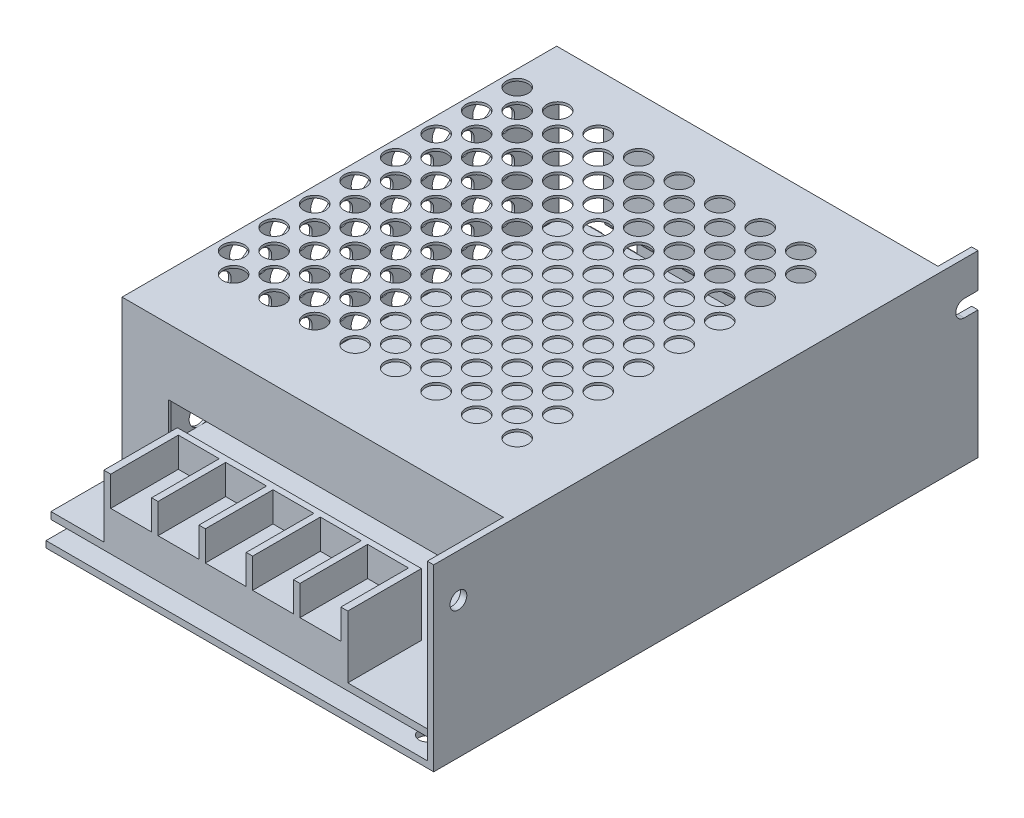
SolidWorks part; units mm, degrees
material "1060 Alloy"
ref_plane "Front Plane" through (0, 0, 0) normal (0, 0, 1) x (1, 0, 0)
ref_plane "Top Plane" through (0, 0, 0) normal (0, 1, 0) x (1, 0, 0)
ref_plane "Right Plane" through (0, 0, 0) normal (1, 0, 0) x (0, 0, -1)
sketch "Sketch1" plane through (0, 0, 0) normal (0, 0, 1) x (1, 0, 0)
  line L0 (0, 0) -> (0, 36.3)
  line L1 (0, 0) -> (-78.5, 0)
  line L2 (-78.5, 0) -> (-78.5, 1.3)
  line L3 (-78.5, 1.3) -> (-1.3, 1.3)
  line L4 (-1.3, 1.3) -> (-1.3, 36.3)
  line L5 (-1.3, 36.3) -> (0, 36.3)
  dimension "D1" = 1.3
  dimension "D2" = 36.3
  dimension "D3" = 78.5
extrude "Base Boss-Extrude1" add sketch "Sketch1" against normal blind 110.2
sketch "Sketch2" plane through (-1.3, 0, 0) normal (-1, 0, 0) x (0, 0, 1)
  line L0 (-110.2, 36.3) -> (0, 36.3) construction
  line L1 (0, 36.3) -> (0, 1.3) construction
  line L2 (-110.2, 36.3) -> (-110.2, 1.3) construction
  line L3 (-110.2, 29.3) -> (-107.4, 29.3)
  line L4 (-110.2, 29.3) -> (-110.2, 25.9)
  line L5 (-110.2, 25.9) -> (-107.4, 25.9)
  line L6 (-107.4, 29.3) -> (-107.4, 25.9) construction
  circle A0 centre (-5, 27.6) radius 1.7
  arc A1 (-107.4, 29.3) -> (-107.4, 25.9) centre (-107.4, 27.6) cw
  arc A2 (-107.4, 25.9) -> (-107.4, 29.3) centre (-107.4, 27.6) cw construction
  dimension "D1" = 3.4
  dimension "D2" = 7
  dimension "D3" = 3.3
  dimension "D4" = 3.4
  dimension "D5" = 7
  dimension "D6" = 4.5
extrude "Mounting Holes Side Cut-Extrude1" cut sketch "Sketch2" against normal up to surface (1.3 mm away) up to face at (0, 18.15, -55.1)
sketch "Sketch3" plane through (0, 1.3, 0) normal (0, 1, 0) x (1, 0, 0)
  line L0 (-1.3, 110.2) -> (-78.5, 110.2) construction
  line L1 (-72.7, 108.5) -> (-76.1, 108.5) construction
  line L2 (-72.7, 108.5) -> (-72.7, 110.2)
  line L3 (-72.7, 110.2) -> (-76.1, 110.2)
  line L4 (-76.1, 108.5) -> (-76.1, 110.2)
  line L5 (-78.5, 110.2) -> (-78.5, 0) construction
  line L7 (-5.8, 4.5) -> (-5.8, 0) construction
  line L8 (-1.3, 0) -> (-78.5, 0) construction
  line L9 (-5.8, 4.5) -> (-1.3, 4.5) construction
  line L10 (-1.3, 110.2) -> (-1.3, 0) construction
  circle A0 centre (-5.8, 4.5) radius 1.7
  arc A1 (-72.7, 108.5) -> (-76.1, 108.5) centre (-74.4, 108.5) cw
  arc A2 (-72.7, 108.5) -> (-76.1, 108.5) centre (-74.4, 108.5) ccw construction
  dimension "D1" = 3.4
  dimension "D2" = 2.8
  dimension "D3" = 2.8
  dimension "D4" = 106.8
  dimension "D5" = 2.4
extrude "Mounting Holes Bottom Cut-Extrude2" cut sketch "Sketch3" against normal up to surface (1.3 mm away) up to face at (-39.25, 0, -55.1)
sketch "Sketch4" plane through (-1.3, 0, 0) normal (-1, 0, 0) x (0, 0, 1)
  line L0 (-110.2, 36.3) -> (0, 36.3) construction
  line L1 (-110.2, 1.3) -> (-108.9, 1.3)
  line L2 (-110.2, 1.3) -> (-110.2, 8.3)
  line L3 (-110.2, 8.3) -> (-108.9, 8.3) construction
  line L4 (-108.9, 1.3) -> (-108.9, 8.3)
  line L5 (-103.4, 36.3) -> (-102.1, 36.3)
  line L6 (-103.4, 36.3) -> (-103.4, 12)
  line L7 (-103.4, 12) -> (-102.1, 12) construction
  line L8 (-102.1, 36.3) -> (-102.1, 12)
  line L9 (-108.8113, 10.1098) -> (-103.8252, 11.4459)
  line L10 (-108.4748, 8.8541) -> (-103.4887, 10.1902)
  line L11 (-106.3182, 10.7779) -> (-105.9818, 9.5221) construction
  line L12 (-110.2, 25.9) -> (-110.2, 1.3) construction
  arc A0 (-108.9, 8.3) -> (-108.4748, 8.8541) centre (-108.3263, 8.3) cw
  arc A1 (-110.2, 8.3) -> (-108.8113, 10.1098) centre (-108.3263, 8.3) cw
  arc A2 (-103.8252, 11.4459) -> (-103.4, 12) centre (-103.9737, 12) ccw
  arc A3 (-103.4887, 10.1902) -> (-102.1, 12) centre (-103.9737, 12) ccw
  dimension "D1" = 1.3
  dimension "D2" = 6.8
  dimension "D3" = 7
  dimension "D4" = 24.3
  dimension "D5" = 15
extrude "Heatsink Boss-Extrude2" add sketch "Sketch4" along normal blind 66.4
sketch "Sketch5" plane through (0, 0, -103.4) normal (0, 0, -1) x (-1, 0, 0)
  line L1 (1.3, 36.3) -> (78.5, 36.3)
  line L2 (1.3, 36.3) -> (1.3, 35.8)
  line L3 (1.3, 35.8) -> (78, 35.8)
  line L5 (78.5, 1.3) -> (78, 1.3)
  line L6 (78.5, 1.3) -> (78.5, 36.3)
  line L8 (78, 1.3) -> (78, 35.8)
  dimension "D1" = 0.5
extrude "Chassi Boss-Extrude3" add sketch "Sketch5" against normal blind 88
sketch "Sketch6" plane through (0, 0, -15.4) normal (0, 0, 1) x (1, 0, 0)
  line L1 (-1.3, 36.3) -> (-78.5, 36.3)
  line L2 (-1.3, 36.3) -> (-1.3, 23)
  line L3 (-1.3, 23) -> (-69.1, 23)
  line L6 (-78.5, 1.3) -> (-69.1, 1.3)
  line L7 (-78.5, 1.3) -> (-78.5, 36.3)
  line L9 (-69.1, 1.3) -> (-69.1, 23)
  dimension "D1" = 13.3
  dimension "D2" = 9.4
extrude "Chassi Front Boss-Extrude4" add sketch "Sketch6" against normal blind 0.5
ref_plane "PCB Plane1" through (0, 5, 0) normal (0, 1, 0) x (1, 0, 0)
sketch "Sketch7" plane through (0, 5, 0) normal (0, 1, 0) x (1, 0, 0)
  line L0 (-1.3, 108.9) -> (-1.3, 0) construction
  line L1 (-1.3, 0.5) -> (-78, 0.5)
  line L2 (-1.3, 0.5) -> (-1.3, 105)
  line L3 (-1.3, 105) -> (-78, 105)
  line L4 (-78, 0.5) -> (-78, 105)
  line L5 (-78, 15.9) -> (-78, 103.4) construction
  line L7 (-67.7, 110.2) -> (-72.7, 110.2) construction
  line L8 (-1.3, 0) -> (-78.5, 0) construction
  point P8 (-70.2, 110.2)
  dimension "D1" = 5.2
  dimension "D2" = 0.5
extrude "PCB Boss-Extrude5" add sketch "Sketch7" along normal blind 1.4
sketch "Sketch8" plane through (0, 6.4, 0) normal (0, 1, 0) x (1, 0, 0)
  line L0 (-78, 0.5) -> (-1.3, 0.5) construction
  line L1 (-67.3, 0.5) -> (-17.9, 0.5)
  line L2 (-67.3, 0.5) -> (-67.3, 15.4)
  line L3 (-67.3, 15.4) -> (-17.9, 15.4)
  line L4 (-17.9, 0.5) -> (-17.9, 15.4)
  line L5 (-78.5, 15.4) -> (-1.3, 15.4) construction
  line L6 (-1.3, 0.5) -> (-1.3, 105) construction
  line L7 (-78.5, 15.4) -> (-78.5, 0) construction
  dimension "D1" = 49.4
  dimension "D2" = 16.6
  dimension "D3" = 11.2
extrude "Connector Housing Boss-Extrude6" add sketch "Sketch8" along normal blind 12.6
sketch "Sketch9" plane through (0, 19, 0) normal (0, 1, 0) x (1, 0, 0)
  line L0 (-67.3, 0.5) -> (-17.9, 0.5) construction
  line L1 (-65.9, 0.5) -> (-57.62, 0.5)
  line L2 (-65.9, 0.5) -> (-65.9, 14.2)
  line L3 (-65.9, 14.2) -> (-57.62, 14.2)
  line L4 (-57.62, 0.5) -> (-57.62, 14.2)
  line L5 (-67.3, 14.2) -> (-65.9, 14.2) construction
  line L6 (-56.32, 14.2) -> (-48.04, 14.2)
  line L7 (-56.32, 14.2) -> (-56.32, 0.5)
  line L8 (-56.32, 0.5) -> (-48.04, 0.5)
  line L9 (-48.04, 14.2) -> (-48.04, 0.5)
  line L10 (-46.74, 0.5) -> (-38.46, 0.5)
  line L11 (-46.74, 0.5) -> (-46.74, 14.2)
  line L12 (-46.74, 14.2) -> (-38.46, 14.2)
  line L13 (-38.46, 0.5) -> (-38.46, 14.2)
  line L14 (-37.16, 14.2) -> (-28.88, 14.2)
  line L15 (-37.16, 14.2) -> (-37.16, 0.5)
  line L16 (-37.16, 0.5) -> (-28.88, 0.5)
  line L17 (-28.88, 14.2) -> (-28.88, 0.5)
  line L18 (-27.58, 14.2) -> (-19.3, 14.2)
  line L19 (-27.58, 14.2) -> (-27.58, 0.5)
  line L20 (-27.58, 0.5) -> (-19.3, 0.5)
  line L21 (-19.3, 14.2) -> (-19.3, 0.5)
  line L22 (-67.3, 15.4) -> (-67.3, 0.5) construction
  line L23 (-19.3, 14.2) -> (-17.9, 14.2) construction
  line L24 (-17.9, 0.5) -> (-17.9, 15.4) construction
  line L25 (-27.58, 14.2) -> (-28.88, 14.2) construction
  line L26 (-37.16, 14.2) -> (-38.46, 14.2) construction
  line L27 (-46.74, 14.2) -> (-48.04, 14.2) construction
  line L28 (-56.32, 14.2) -> (-57.62, 14.2) construction
  dimension "D1" = 1.3
  dimension "D2" = 1.4
  dimension "D3" = 13.7
extrude "Connector Screw Cut-Extrude3" cut sketch "Sketch9" against normal blind 6
sketch "Sketch10" plane through (0, 36.3, 0) normal (0, 1, 0) x (1, 0, 0)
  line L0 (-78.5, 92.2) -> (0, 92.2) construction
  line L1 (-78.5, 15.4) -> (-78.5, 103.4) construction
  line L2 (0, 110.2) -> (0, 0) construction
  line L3 (-75.3, 103.4) -> (-75.3, 15.4) construction
  line L4 (-78.5, 103.4) -> (-1.3, 103.4) construction
  line L5 (-78.5, 15.4) -> (-1.3, 15.4) construction
  line L6 (-75.3, 88.0988) -> (0, 88.0988) construction
  line L7 (-71.1988, 92.2) -> (-71.1988, 15.4) construction
  line L8 (-71.1988, 88.0988) -> (-75.3, 92.2) construction
  line L9 (-71.1988, 88.0988) -> (-67.0976, 92.2) construction
  line L10 (-71.1988, 88.0988) -> (-75.3, 83.9976) construction
  circle A0 centre (-75.3, 92.2) radius 2.2
  circle A1 centre (-71.1988, 88.0988) radius 2.2
  circle A2 centre (-67.0976, 92.2) radius 2.2
  circle A3 centre (-62.9963, 88.0988) radius 2.2
  circle A4 centre (-58.8951, 92.2) radius 2.2
  circle A5 centre (-54.7939, 88.0988) radius 2.2
  circle A6 centre (-50.6927, 92.2) radius 2.2
  circle A7 centre (-46.5915, 88.0988) radius 2.2
  circle A8 centre (-42.4902, 92.2) radius 2.2
  circle A9 centre (-38.389, 88.0988) radius 2.2
  circle A10 centre (-34.2878, 92.2) radius 2.2
  circle A11 centre (-30.1866, 88.0988) radius 2.2
  circle A12 centre (-26.0854, 92.2) radius 2.2
  circle A13 centre (-21.9841, 88.0988) radius 2.2
  circle A14 centre (-67.0976, 83.9976) radius 2.2
  circle A15 centre (-62.9963, 79.8963) radius 2.2
  circle A16 centre (-58.8951, 83.9976) radius 2.2
  circle A17 centre (-54.7939, 79.8963) radius 2.2
  circle A18 centre (-50.6927, 83.9976) radius 2.2
  circle A19 centre (-46.5915, 79.8963) radius 2.2
  circle A20 centre (-42.4902, 83.9976) radius 2.2
  circle A21 centre (-38.389, 79.8963) radius 2.2
  circle A22 centre (-34.2878, 83.9976) radius 2.2
  circle A23 centre (-30.1866, 79.8963) radius 2.2
  circle A24 centre (-26.0854, 83.9976) radius 2.2
  circle A25 centre (-21.9841, 79.8963) radius 2.2
  circle A26 centre (-67.0976, 75.7951) radius 2.2
  circle A27 centre (-62.9963, 71.6939) radius 2.2
  circle A28 centre (-58.8951, 75.7951) radius 2.2
  circle A29 centre (-54.7939, 71.6939) radius 2.2
  circle A30 centre (-50.6927, 75.7951) radius 2.2
  circle A31 centre (-46.5915, 71.6939) radius 2.2
  circle A32 centre (-42.4902, 75.7951) radius 2.2
  circle A33 centre (-38.389, 71.6939) radius 2.2
  circle A34 centre (-34.2878, 75.7951) radius 2.2
  circle A35 centre (-30.1866, 71.6939) radius 2.2
  circle A36 centre (-26.0854, 75.7951) radius 2.2
  circle A37 centre (-21.9841, 71.6939) radius 2.2
  circle A38 centre (-67.0976, 67.5927) radius 2.2
  circle A39 centre (-62.9963, 63.4915) radius 2.2
  circle A40 centre (-58.8951, 67.5927) radius 2.2
  circle A41 centre (-54.7939, 63.4915) radius 2.2
  circle A42 centre (-50.6927, 67.5927) radius 2.2
  circle A43 centre (-46.5915, 63.4915) radius 2.2
  circle A44 centre (-42.4902, 67.5927) radius 2.2
  circle A45 centre (-38.389, 63.4915) radius 2.2
  circle A46 centre (-34.2878, 67.5927) radius 2.2
  circle A47 centre (-30.1866, 63.4915) radius 2.2
  circle A48 centre (-26.0854, 67.5927) radius 2.2
  circle A49 centre (-21.9841, 63.4915) radius 2.2
  circle A50 centre (-67.0976, 59.3902) radius 2.2
  circle A51 centre (-62.9963, 55.289) radius 2.2
  circle A52 centre (-58.8951, 59.3902) radius 2.2
  circle A53 centre (-54.7939, 55.289) radius 2.2
  circle A54 centre (-50.6927, 59.3902) radius 2.2
  circle A55 centre (-46.5915, 55.289) radius 2.2
  circle A56 centre (-42.4902, 59.3902) radius 2.2
  circle A57 centre (-38.389, 55.289) radius 2.2
  circle A58 centre (-34.2878, 59.3902) radius 2.2
  circle A59 centre (-30.1866, 55.289) radius 2.2
  circle A60 centre (-26.0854, 59.3902) radius 2.2
  circle A61 centre (-21.9841, 55.289) radius 2.2
  circle A62 centre (-67.0976, 51.1878) radius 2.2
  circle A63 centre (-62.9963, 47.0866) radius 2.2
  circle A64 centre (-58.8951, 51.1878) radius 2.2
  circle A65 centre (-54.7939, 47.0866) radius 2.2
  circle A66 centre (-50.6927, 51.1878) radius 2.2
  circle A67 centre (-46.5915, 47.0866) radius 2.2
  circle A68 centre (-42.4902, 51.1878) radius 2.2
  circle A69 centre (-38.389, 47.0866) radius 2.2
  circle A70 centre (-34.2878, 51.1878) radius 2.2
  circle A71 centre (-30.1866, 47.0866) radius 2.2
  circle A72 centre (-26.0854, 51.1878) radius 2.2
  circle A73 centre (-21.9841, 47.0866) radius 2.2
  circle A74 centre (-67.0976, 42.9854) radius 2.2
  circle A75 centre (-62.9963, 38.8841) radius 2.2
  circle A76 centre (-58.8951, 42.9854) radius 2.2
  circle A77 centre (-54.7939, 38.8841) radius 2.2
  circle A78 centre (-50.6927, 42.9854) radius 2.2
  circle A79 centre (-46.5915, 38.8841) radius 2.2
  circle A80 centre (-42.4902, 42.9854) radius 2.2
  circle A81 centre (-38.389, 38.8841) radius 2.2
  circle A82 centre (-34.2878, 42.9854) radius 2.2
  circle A83 centre (-30.1866, 38.8841) radius 2.2
  circle A84 centre (-26.0854, 42.9854) radius 2.2
  circle A85 centre (-21.9841, 38.8841) radius 2.2
  circle A86 centre (-75.3, 83.9976) radius 2.2
  circle A87 centre (-71.1988, 79.8963) radius 2.2
  circle A88 centre (-75.3, 75.7951) radius 2.2
  circle A89 centre (-71.1988, 71.6939) radius 2.2
  circle A90 centre (-75.3, 67.5927) radius 2.2
  circle A91 centre (-71.1988, 63.4915) radius 2.2
  circle A92 centre (-75.3, 59.3902) radius 2.2
  circle A93 centre (-71.1988, 55.289) radius 2.2
  circle A94 centre (-75.3, 51.1878) radius 2.2
  circle A95 centre (-71.1988, 47.0866) radius 2.2
  circle A96 centre (-75.3, 42.9854) radius 2.2
  circle A97 centre (-71.1988, 38.8841) radius 2.2
  circle A98 centre (-75.3, 34.7829) radius 2.2
  circle A99 centre (-71.1988, 30.6817) radius 2.2
  circle A100 centre (-67.0976, 34.7829) radius 2.2
  circle A101 centre (-62.9963, 30.6817) radius 2.2
  circle A102 centre (-58.8951, 34.7829) radius 2.2
  circle A103 centre (-54.7939, 30.6817) radius 2.2
  circle A104 centre (-50.6927, 34.7829) radius 2.2
  circle A105 centre (-46.5915, 30.6817) radius 2.2
  circle A106 centre (-42.4902, 34.7829) radius 2.2
  circle A107 centre (-38.389, 30.6817) radius 2.2
  circle A108 centre (-34.2878, 34.7829) radius 2.2
  circle A109 centre (-30.1866, 30.6817) radius 2.2
  circle A110 centre (-26.0854, 34.7829) radius 2.2
  circle A111 centre (-21.9841, 30.6817) radius 2.2
  circle A112 centre (-17.8829, 92.2) radius 2.2
  circle A113 centre (-13.7817, 88.0988) radius 2.2
  circle A114 centre (-17.8829, 83.9976) radius 2.2
  circle A115 centre (-13.7817, 79.8963) radius 2.2
  circle A116 centre (-17.8829, 75.7951) radius 2.2
  circle A117 centre (-13.7817, 71.6939) radius 2.2
  circle A118 centre (-17.8829, 67.5927) radius 2.2
  circle A119 centre (-13.7817, 63.4915) radius 2.2
  circle A120 centre (-17.8829, 59.3902) radius 2.2
  circle A121 centre (-13.7817, 55.289) radius 2.2
  circle A122 centre (-17.8829, 51.1878) radius 2.2
  circle A123 centre (-13.7817, 47.0866) radius 2.2
  circle A124 centre (-17.8829, 42.9854) radius 2.2
  circle A125 centre (-13.7817, 38.8841) radius 2.2
  circle A126 centre (-17.8829, 34.7829) radius 2.2
  circle A127 centre (-13.7817, 30.6817) radius 2.2
  dimension "D1" = 4.4
  dimension "D2" = 1
  dimension "D3" = 9
  dimension "D5" = 1.4
  dimension "D4" = 45
  dimension "D6" = 8
  dimension "D7" = 8
sketch "Sketch11" plane through (-78.5, 0, 0) normal (-1, 0, 0) x (0, 0, 1)
  line L0 (-92.2, 36.3) -> (-92.2, 0) construction
  line L1 (-15.4, 36.3) -> (-103.4, 36.3) construction
  line L2 (-110.2, 0) -> (0, 0) construction
  line L3 (-103.4, 33.1) -> (-15.4, 33.1) construction
  line L4 (-103.4, 1.3) -> (-103.4, 36.3) construction
  line L5 (-15.4, 1.3) -> (-15.4, 36.3) construction
  line L6 (-88.0988, 36.3) -> (-88.0988, 0) construction
  line L7 (-103.4, 28.9988) -> (-15.4, 28.9988) construction
  line L8 (-88.0988, 33.1) -> (-92.2, 28.9988) construction
  line L10 (-88.0988, 33.1) -> (-83.9976, 28.9988) construction
  line L11 (-92.2, 28.9988) -> (-88.0988, 24.8976) construction
  circle A0 centre (-88.0988, 33.1) radius 2.2
  circle A1 centre (-92.2, 28.9988) radius 2.2
  circle A2 centre (-83.9976, 28.9988) radius 2.2
  circle A3 centre (-79.8963, 33.1) radius 2.2
  circle A4 centre (-75.7951, 28.9988) radius 2.2
  circle A5 centre (-71.6939, 33.1) radius 2.2
  circle A6 centre (-67.5927, 28.9988) radius 2.2
  circle A7 centre (-63.4915, 33.1) radius 2.2
  circle A8 centre (-59.3902, 28.9988) radius 2.2
  circle A9 centre (-55.289, 33.1) radius 2.2
  circle A10 centre (-51.1878, 28.9988) radius 2.2
  circle A11 centre (-47.0866, 33.1) radius 2.2
  circle A12 centre (-42.9854, 28.9988) radius 2.2
  circle A13 centre (-38.8841, 33.1) radius 2.2
  circle A14 centre (-34.7829, 28.9988) radius 2.2
  circle A15 centre (-30.6817, 33.1) radius 2.2
  circle A16 centre (-83.9976, 20.7963) radius 2.2
  circle A17 centre (-79.8963, 24.8976) radius 2.2
  circle A18 centre (-75.7951, 20.7963) radius 2.2
  circle A19 centre (-71.6939, 24.8976) radius 2.2
  circle A20 centre (-67.5927, 20.7963) radius 2.2
  circle A21 centre (-63.4915, 24.8976) radius 2.2
  circle A22 centre (-59.3902, 20.7963) radius 2.2
  circle A23 centre (-55.289, 24.8976) radius 2.2
  circle A24 centre (-51.1878, 20.7963) radius 2.2
  circle A25 centre (-47.0866, 24.8976) radius 2.2
  circle A26 centre (-42.9854, 20.7963) radius 2.2
  circle A27 centre (-38.8841, 24.8976) radius 2.2
  circle A28 centre (-34.7829, 20.7963) radius 2.2
  circle A29 centre (-30.6817, 24.8976) radius 2.2
  circle A30 centre (-83.9976, 12.5939) radius 2.2
  circle A31 centre (-79.8963, 16.6951) radius 2.2
  circle A32 centre (-75.7951, 12.5939) radius 2.2
  circle A33 centre (-71.6939, 16.6951) radius 2.2
  circle A34 centre (-67.5927, 12.5939) radius 2.2
  circle A35 centre (-63.4915, 16.6951) radius 2.2
  circle A36 centre (-59.3902, 12.5939) radius 2.2
  circle A37 centre (-55.289, 16.6951) radius 2.2
  circle A38 centre (-51.1878, 12.5939) radius 2.2
  circle A39 centre (-47.0866, 16.6951) radius 2.2
  circle A40 centre (-42.9854, 12.5939) radius 2.2
  circle A41 centre (-38.8841, 16.6951) radius 2.2
  circle A42 centre (-34.7829, 12.5939) radius 2.2
  circle A43 centre (-30.6817, 16.6951) radius 2.2
  circle A44 centre (-83.9976, 4.3915) radius 2.2
  circle A45 centre (-79.8963, 8.4927) radius 2.2
  circle A46 centre (-75.7951, 4.3915) radius 2.2
  circle A47 centre (-71.6939, 8.4927) radius 2.2
  circle A48 centre (-67.5927, 4.3915) radius 2.2
  circle A49 centre (-63.4915, 8.4927) radius 2.2
  circle A50 centre (-59.3902, 4.3915) radius 2.2
  circle A51 centre (-55.289, 8.4927) radius 2.2
  circle A52 centre (-51.1878, 4.3915) radius 2.2
  circle A53 centre (-47.0866, 8.4927) radius 2.2
  circle A54 centre (-42.9854, 4.3915) radius 2.2
  circle A55 centre (-38.8841, 8.4927) radius 2.2
  circle A56 centre (-34.7829, 4.3915) radius 2.2
  circle A57 centre (-30.6817, 8.4927) radius 2.2
  circle A58 centre (-92.2, 20.7963) radius 2.2
  circle A59 centre (-88.0988, 24.8976) radius 2.2
  circle A60 centre (-92.2, 12.5939) radius 2.2
  circle A61 centre (-88.0988, 16.6951) radius 2.2
  circle A62 centre (-92.2, 4.3915) radius 2.2
  circle A63 centre (-88.0988, 8.4927) radius 2.2
  dimension "D2" = 1.4
  dimension "D3" = 4.4
  dimension "D4" = 1
  dimension "D1" = 45
  dimension "D5" = 8
  dimension "D6" = 4
extrude "Chassi Venting Holes Top Cut-Extrude5" cut sketch "Sketch10" against normal up to surface (0.5 mm away) up to face at (-49, 35.8, -73.8)
extrude "Chassi Venting Holes Side Cut-Extrude6" cut sketch "Sketch11" against normal up to surface (0.5 mm away) up to face at (-78, 21.1, -59.65)
